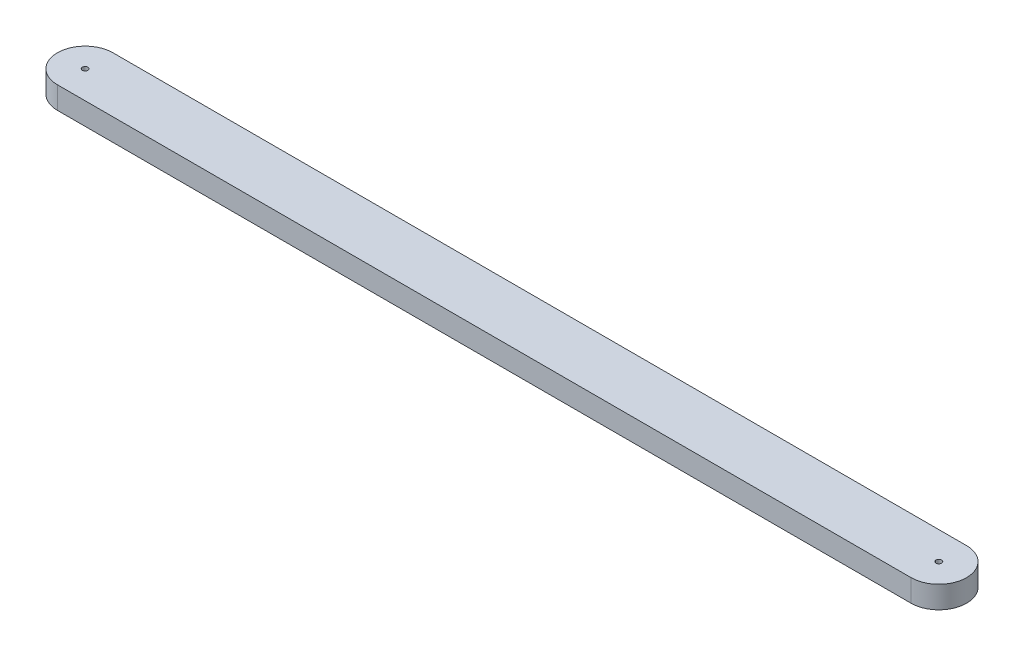
SolidWorks part; units mm, degrees
material "6061-T4 (SS)"
ref_plane "Front Plane" through (0, 0, 0) normal (0, 0, 1) x (1, 0, 0)
ref_plane "Top Plane" through (0, 0, 0) normal (0, 1, 0) x (1, 0, 0)
ref_plane "Right Plane" through (0, 0, 0) normal (1, 0, 0) x (0, 0, -1)
sketch "Sketch1" plane through (0, 0, 0) normal (0, 1, 0) x (1, 0, 0)
  line L0 (-76.94, -5) -> (-76.94, 5)
  line L1 (-76.94, -5) -> (76.94, -5)
  line L2 (-76.94, 5) -> (76.94, 5)
  line L3 (76.94, -5) -> (76.94, 5)
  line L4 (-76.94, -5) -> (76.94, 5) construction
  line L5 (-76.94, 5) -> (76.94, -5) construction
  arc A0 (-76.94, 5) -> (-76.94, -5) centre (-76.94, 0) ccw
  arc A1 (76.94, 5) -> (76.94, -5) centre (76.94, 0) cw
  circle A2 centre (-76.94, 0) radius 0.5
  circle A3 centre (76.94, 0) radius 0.5
  point P1 (0, 0)
  dimension "D1" = 153.88
  dimension "D2" = 10
extrude "Boss-Extrude1" add sketch "Sketch1" along normal blind 2 and the other way blind 2 contours L1 L3 L2 L0 | L0 A0 | A1 L3 region at (-79.0814, 0, 0) region at (0, 0, 0) region at (79.0814, 0, 0)
